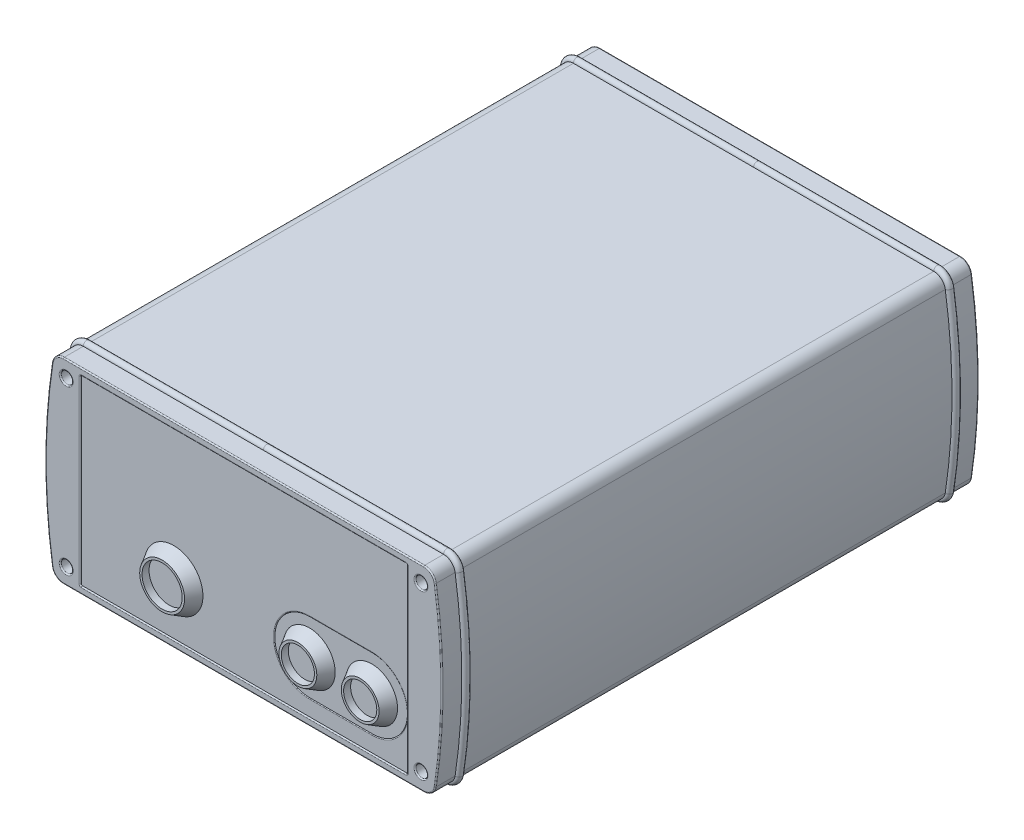
SolidWorks part; units mm, degrees
material "ABS"
ref_plane "Front Plane" through (0, 0, 0) normal (0, 0, 1) x (1, 0, 0)
ref_plane "Top Plane" through (0, 0, 0) normal (0, 1, 0) x (1, 0, 0)
ref_plane "Right Plane" through (0, 0, 0) normal (1, 0, 0) x (0, 0, -1)
sketch "Sketch1" plane through (0, 0, 0) normal (0, 0, 1) x (1, 0, 0)
  line L1 (0, 0) -> (172, 0)
  line L2 (0, 0) -> (0, 84)
  line L3 (0, 84) -> (172, 84)
  line L4 (172, 0) -> (172, 84)
  dimension "D1" = 84
  dimension "D2" = 172
extrude "Boss-Extrude1" add sketch "Sketch1" along normal blind 230
sketch "Sketch2" plane through (0, 0, 230) normal (0, 0, 1) x (1, 0, 0)
  line L0 (0, 42) -> (172, 42) construction
  line L1 (0, 84) -> (0, 0) construction
  line L2 (172, 0) -> (172, 84) construction
  line L4 (-106.1336, 127.5793) -> (16.1039, 127.5793)
  line L5 (-106.1336, 127.5793) -> (-106.1336, -44.765)
  line L6 (-106.1336, -44.765) -> (16.5393, -44.765)
  arc A0 (16.1039, 127.5793) -> (16.5393, -44.765) centre (251, 42) ccw
  dimension "D1" = 500
  dimension "D2" = 251
extrude "Cut-Extrude1" cut sketch "Sketch2" against normal through all
ref_plane "Plane1" through (86, 0, 0) normal (1, 0, 0) x (0, 0, -1)
mirror "Mirror1" about plane through (86, 0, 0) normal (1, 0, 0) of "Cut-Extrude1"
fillet "Fillet1" radius 5 4 edges at (4.5533, 0, 115) (167.4467, 0, 115) (167.4467, 84, 115) (4.5533, 84, 115)
ref_plane "Plane2" through (0, 0, 220) normal (0, 0, 1) x (1, 0, 0)
sketch "Sketch3" plane through (0, 0, 220) normal (0, 0, 1) x (1, 0, 0)
  line L2 (8.81, 0) -> (163.19, 0)
  line L3 (163.19, 84) -> (8.81, 84)
  line L4 (8.81, 0) -> (163.19, 0)
  line L5 (163.19, 84) -> (8.81, 84)
  arc A6 (3.8673, 79.7551) -> (3.8673, 4.2449) centre (251, 42) ccw
  arc A7 (3.8673, 4.2449) -> (8.81, 0) centre (8.81, 5) ccw
  arc A8 (163.19, 0) -> (168.1327, 4.2449) centre (163.19, 5) ccw
  arc A9 (168.1327, 4.2449) -> (168.1327, 79.7551) centre (-79, 42) ccw
  arc A10 (168.1327, 79.7551) -> (163.19, 84) centre (163.19, 79) ccw
  arc A11 (8.81, 84) -> (3.8673, 79.7551) centre (8.81, 79) ccw
  arc A12 (3.8673, 79.7551) -> (3.8673, 4.2449) centre (251, 42) ccw
  arc A13 (3.8673, 4.2449) -> (8.81, 0) centre (8.81, 5) ccw
  arc A14 (163.19, 0) -> (168.1327, 4.2449) centre (163.19, 5) ccw
  arc A15 (168.1327, 4.2449) -> (168.1327, 79.7551) centre (-79, 42) ccw
  arc A16 (168.1327, 79.7551) -> (163.19, 84) centre (163.19, 79) ccw
  arc A17 (8.81, 84) -> (3.8673, 79.7551) centre (8.81, 79) ccw
  dimension "D1" = 0
sketch "Sketch4" plane through (86, 0, 0) normal (1, 0, 0) x (0, 0, -1)
  line L0 (-220, 84) -> (-220, 79.7551) construction
  line L1 (0, 84) -> (-230, 84) construction
  line L2 (-218.5, 84) -> (-221.5, 84)
  arc A0 (-218.5, 84) -> (-221.5, 84) centre (-220, 84) ccw
  dimension "D1" = 3
sweep "Sweep1" add profiles "Sketch4" path "Sketch3"
ref_plane "Plane3" through (0, 0, 115) normal (0, 0, 1) x (1, 0, 0)
mirror "Mirror2" about plane through (0, 0, 115) normal (0, 0, 1) of "Sweep1"
sketch "Sketch5" plane through (0, 0, 230) normal (0, 0, 1) x (1, 0, 0)
  line L0 (163.19, 84) -> (8.81, 84) construction
  line L1 (16, 81) -> (156, 81)
  line L2 (16, 81) -> (16, 3)
  line L3 (16, 3) -> (156, 3)
  line L4 (156, 81) -> (156, 3)
  line L5 (8.81, 0) -> (163.19, 0) construction
  arc A0 (169.6155, 4.0184) -> (169.6155, 79.9816) centre (-79, 42) ccw construction
  arc A1 (2.3845, 79.9816) -> (2.3845, 4.0184) centre (251, 42) ccw construction
  dimension "D1" = 3
  dimension "D2" = 3
  dimension "D3" = 235
  dimension "D4" = 235
extrude "Cut-Extrude2" cut sketch "Sketch5" against normal blind 0.5 contours L2 L3 L4 L1
fillet "Fillet2" radius 0.5 4 edges at (86, 3, 230) (156, 42, 230) (16, 42, 230) (86, 81, 230)
fillet "Fillet3" radius 0.5 16 edges at (166.4477, 82.7931, 0) (171, 42, 0) (166.4477, 1.2069, 0) (86, 0, 0) (5.5523, 1.2069, 0) (1, 42, 0) (5.5523, 82.7931, 0) (166.4477, 1.2069, 230) (86, 0, 230) (5.5523, 1.2069, 230) (1, 42, 230) (5.5523, 82.7931, 230) (86, 84, 230) (166.4477, 82.7931, 230) (86, 84, 0) (171, 42, 230)
sketch "Sketch6" plane through (0, 0, 230) normal (0, 0, 1) x (1, 0, 0)
  circle A0 centre (10, 77) radius 2.5
  dimension "D1" = 5
  dimension "D2" = 10
  dimension "D3" = 77
extrude "Cut-Extrude3" cut sketch "Sketch6" against normal blind 5
mirror "Mirror3" about plane through (86, 0, 0) normal (1, 0, 0) of "Cut-Extrude3"
ref_plane "Plane4" through (0, 42, 0) normal (0, 1, 0) x (1, 0, 0)
mirror "Mirror4" about plane through (0, 42, 0) normal (0, 1, 0) of "Mirror3", "Cut-Extrude3"
fillet "Fillet4" radius 0.5 4 edges at (159.5, 77, 230) (159.5, 7, 230) (12.5, 7, 230) (12.5, 77, 230)
sketch "Sketch7" plane through (0, 0, 229.5) normal (0, 0, 1) x (1, 0, 0)
  circle A0 centre (113.7586, 24.9849) radius 11
  circle A1 centre (140.4617, 24.9849) radius 11
  circle A2 centre (55.6051, 24.9849) radius 12.5
  dimension "D1" = 22
  dimension "D2" = 22
  dimension "D3" = 25
extrude "Boss-Extrude3" add sketch "Sketch7" along normal blind 5
chamfer "Chamfer1" distance 5 angle 30 3 edges at (151.4617, 24.9849, 234.5) (124.7586, 24.9849, 234.5) (68.1051, 24.9849, 234.5)
sketch "Sketch8" plane through (0, 0, 229.5) normal (0, 0, 1) x (1, 0, 0)
  line L0 (113.7586, 24.9849) -> (140.4617, 24.9849) construction
  line L1 (113.7586, 40.0446) -> (140.4617, 40.0446)
  line L2 (113.7586, 9.9252) -> (140.4617, 9.9252)
  arc A0 (113.7586, 40.0446) -> (113.7586, 9.9252) centre (113.7586, 24.9849) ccw
  arc A1 (140.4617, 9.9252) -> (140.4617, 40.0446) centre (140.4617, 24.9849) ccw
  point P4 (127.1101, 24.9849)
extrude "Cut-Extrude4" cut sketch "Sketch8" against normal blind 0.2 contours L1 A1 L2 A0
sketch "Sketch9" plane through (0, 0, 234.5) normal (0, 0, 1) x (1, 0, 0)
  circle A0 centre (55.6051, 24.9849) radius 8.6132
  circle A1 centre (55.6051, 24.9849) radius 9.6132 construction
  circle A2 centre (113.7586, 24.9849) radius 7.1132
  circle A3 centre (140.4617, 24.9849) radius 7.1132
  circle A4 centre (140.4617, 24.9849) radius 8.1132 construction
  circle A5 centre (113.7586, 24.9849) radius 8.1132 construction
  dimension "D1" = 1
  dimension "D2" = 1
  dimension "D3" = 1
extrude "Cut-Extrude5" cut sketch "Sketch9" against normal blind 3
fillet "Fillet5" radius 0.5 4 edges at (98.6989, 24.9849, 229.5) (127.1101, 9.9252, 229.5) (155.5214, 24.9849, 229.5) (127.1101, 40.0446, 229.5)
